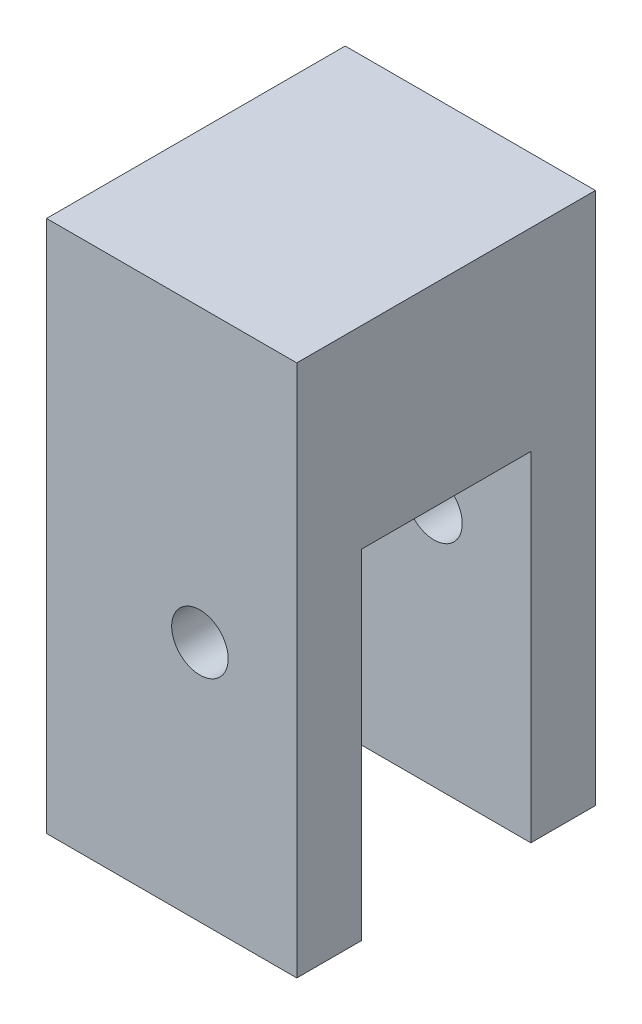
SolidWorks part; units mm, degrees
ref_plane "正面" through (0, 0, 0) normal (0, 0, 1) x (1, 0, 0)
ref_plane "平面" through (0, 0, 0) normal (0, 1, 0) x (1, 0, 0)
ref_plane "右側面" through (0, 0, 0) normal (1, 0, 0) x (0, 0, -1)
sketch "ｽｹｯﾁ1" plane through (0, 0, 0) normal (0, 1, 0) x (1, 0, 0)
  line L0 (0, 18.5) -> (0, 0)
  line L1 (0, -10.175) -> (0, 10.175) construction
  line L2 (0, 0) -> (15.5, 0)
  line L3 (-8.525, 0) -> (8.525, 0) construction
  line L4 (15.5, 0) -> (15.5, 4)
  line L5 (15.5, 4) -> (4, 4)
  line L6 (4, 4) -> (4, 14.5)
  line L7 (4, 14.5) -> (15.5, 14.5)
  line L8 (15.5, 14.5) -> (15.5, 18.5)
  line L9 (15.5, 18.5) -> (0, 18.5)
  dimension "D1" = 4
  dimension "D2" = 4
  dimension "D3" = 10.5
  dimension "D4" = 11.5
  dimension "D5" = 11.5
  dimension "D6" = 4
extrude "ﾎﾞｽ - 押し出し1" add sketch "ｽｹｯﾁ1" along normal blind 21
sketch "ｽｹｯﾁ2" plane through (0, 0, 0) normal (0, 0, 1) x (1, 0, 0)
  line L0 (15.5, 21) -> (15.5, 33)
  line L1 (15.5, 33) -> (0, 33)
  line L2 (0, -10.175) -> (0, 10.175) construction
  line L3 (0, 33) -> (0, 21)
  line L4 (0, 21) -> (15.5, 21) construction
  line L5 (0, 21) -> (15.5, 21)
  dimension "D1" = 12
extrude "ﾎﾞｽ - 押し出し2" add sketch "ｽｹｯﾁ2" against normal blind 18.5
sketch "ｽｹｯﾁ3" plane through (0, 0, 0) normal (0, 0, 1) x (1, 0, 0)
  line L0 (15.5, 33) -> (15.5, 0) construction
  line L1 (15.5, 33) -> (0, 33) construction
  circle A0 centre (9.5, 27) radius 4.25
  dimension "D1" = 8.5
  dimension "D2" = 6
  dimension "D3" = 6
sketch "ｽｹｯﾁ4" plane through (0, 0, 0) normal (0, 0, 1) x (1, 0, 0)
  line L0 (9.5, 0) -> (9.5, 33) construction
  line L1 (8.525, 0) -> (-8.525, 0) construction
  line L2 (15.5, 33) -> (0, 33) construction
  line L3 (15.5, 33) -> (15.5, 0) construction
  circle A0 centre (9.5, 15) radius 1.75
  dimension "D2" = 3.5
  dimension "D3" = 15
  dimension "D1" = 6
extrude "ｶｯﾄ - 押し出し2" cut sketch "ｽｹｯﾁ4" against normal through all
sketch "ｽｹｯﾁ5" [suppressed] plane through (0, 0, 0) normal (-1, 0, 0) x (0, 0, 1)
  line L0 (-18.5, 33) -> (0, 33) construction
  line L1 (-18.5, 33) -> (-18.5, 0) construction
  circle A0 centre (-9.25, 27) radius 4.25
  dimension "D1" = 3.5
  dimension "D3" = 9.25
  dimension "D2" = 6
extrude "ｶｯﾄ - 押し出し3" [suppressed] cut sketch "ｽｹｯﾁ5" against normal through all
sketch "ｽｹｯﾁ6" [suppressed] plane through (4, 0, 0) normal (1, 0, 0) x (0, 0, -1)
  line L0 (8.525, 0) -> (-8.525, 0) construction
  line L1 (4, 21) -> (4, 0) construction
  circle A0 centre (9.25, 5) radius 1.75
  dimension "D1" = 5
  dimension "D2" = 3.5
  dimension "D3" = 5.25
extrude "ｶｯﾄ - 押し出し4" [suppressed] cut sketch "ｽｹｯﾁ6" against normal through all
fillet "ﾌｨﾚｯﾄ1" [suppressed] radius 9
